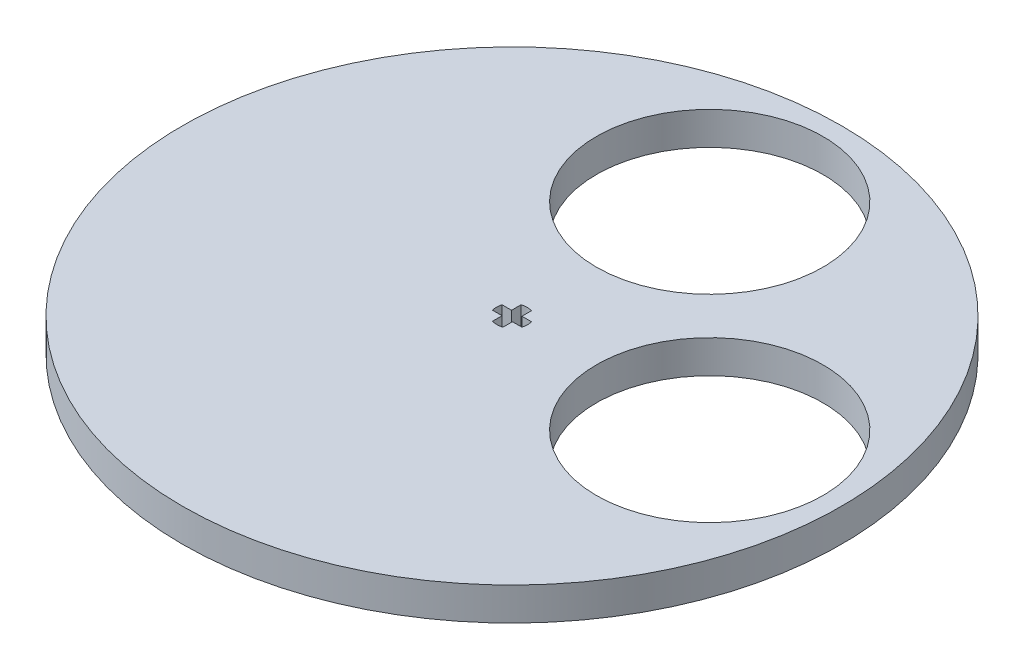
SolidWorks part; units mm, degrees
ref_plane "Front Plane" through (0, 0, 0) normal (0, 0, 1) x (1, 0, 0)
ref_plane "Top Plane" through (0, 0, 0) normal (0, 1, 0) x (1, 0, 0)
ref_plane "Right Plane" through (0, 0, 0) normal (1, 0, 0) x (0, 0, -1)
sketch "Sketch6" plane through (0, 0, 0) normal (0, 1, 0) x (1, 0, 0)
  circle A2 centre (63.5, 63.5) radius 50.8
  dimension "D1" = 101.6
extrude "Boss-Extrude3" add sketch "Sketch6" along normal blind 5.08 contours A2
sketch "Sketch11" plane through (0, 5.08, 0) normal (0, 1, 0) x (1, 0, 0)
  line L0 (63.5, 114.3) -> (63.5, 63.5)
  line L1 (63.5, 63.5) -> (114.3, 63.5)
  circle A0 centre (63.5, 93.98) radius 17.4625
  circle A1 centre (93.98, 63.5) radius 17.4625
  circle A2 centre (63.5, 63.5) radius 50.8 construction
  dimension "D1" = 34.925
  dimension "D2" = 20.32
  dimension "D3" = 20.32
extrude "Cut-Extrude2" cut sketch "Sketch11" against normal through all contours L0 A0 | L0 A0 | L1 A1 | L1 A1 | A0 region at (70.9113, 5.08, -93.98) region at (93.98, 5.08, -70.9113) region at (93.98, 5.08, -56.0887) region at (56.0887, 5.08, -93.98)
sketch "Sketch12" plane through (0, 5.08, 0) normal (0, 1, 0) x (1, 0, 0)
  line L0 (62.7, 64.2314) -> (62.7, 65.6941)
  line L1 (64.3, 65.6941) -> (64.3, 64.2314)
  line L2 (62.7, 64.2314) -> (64.3, 64.2314) construction
  line L3 (62.7, 64.2314) -> (62.7, 62.7686) construction
  line L4 (62.7, 64.2314) -> (61.2373, 64.2314)
  line L5 (61.2373, 62.7686) -> (62.7, 62.7686)
  line L6 (62.7, 62.7686) -> (62.7, 61.3059)
  line L7 (64.3, 61.3059) -> (64.3, 62.7686)
  line L8 (64.3, 62.7686) -> (65.7627, 62.7686)
  line L9 (64.3, 64.2314) -> (65.7627, 64.2314)
  circle A0 centre (63.5, 63.5) radius 2.75
  circle A1 centre (63.5, 63.5) radius 2.5157 construction
  arc A2 (62.7, 65.6941) -> (64.3, 65.6941) centre (63.5, 63.2202) cw
  arc A3 (61.2373, 64.2314) -> (61.2373, 62.7686) centre (63.7323, 63.5) ccw
  arc A4 (62.7, 61.3059) -> (64.3, 61.3059) centre (63.5, 63.7798) ccw
  arc A5 (65.7627, 64.2314) -> (65.7627, 62.7686) centre (63.2677, 63.5) cw
  point P9 (63.5, 64.2314)
  point P23 (61.1323, 63.5)
  point P24 (63.5, 61.1798)
  dimension "D1" = 5.5
  dimension "D4" = 2.6
  dimension "D5" = 5.0313
  dimension "D2" = 1.4627
  dimension "D3" = 1.6
extrude "Cut-Extrude3" cut sketch "Sketch12" against normal through all contours A0
extrude "Boss-Extrude4" add sketch "Sketch12<3>" against normal up to surface (5.08 mm away) up to face at (63.5, 0, -60.75)
sketch "Sketch12<3>" plane through (0, 5.08, 0) normal (0, 1, 0) x (1, 0, 0) same geometry as "Sketch12"
sketch "Sketch13" plane through (0, 5.08, 0) normal (0, 1, 0) x (1, 0, 0)
  circle A0 centre (63.5, 63.5) radius 2.293
